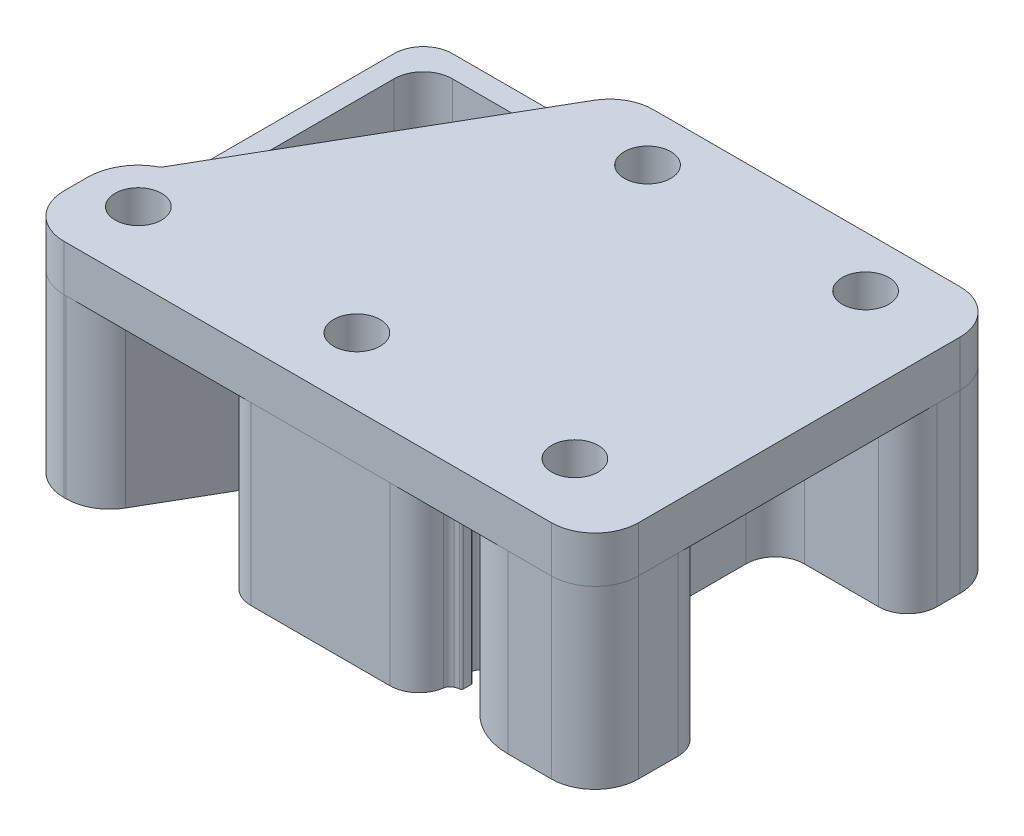
SolidWorks part; units mm, degrees
material "AISI 1045 Steel, cold drawn"
ref_plane "Front Plane" through (0, 0, 0) normal (0, 0, 1) x (1, 0, 0)
ref_plane "Top Plane" through (0, 0, 0) normal (0, 1, 0) x (1, 0, 0)
ref_plane "Right Plane" through (0, 0, 0) normal (1, 0, 0) x (0, 0, -1)
sketch "Sketch1" plane through (0, 0, 0) normal (0, 1, 0) x (1, 0, 0)
  line L0 (-13.5, -13.5) -> (-13.5, -14.619)
  line L1 (7.5, -10) -> (-7.5, -10) construction
  line L2 (7.5, -10) -> (7.5, 10) construction
  line L3 (7.5, 10) -> (-7.5, 10) construction
  line L4 (-7.5, -10) -> (-7.5, 10) construction
  line L5 (7.5, -10) -> (-7.5, 10) construction
  line L6 (7.5, 10) -> (-7.5, -10) construction
  line L7 (13.5, -13.5) -> (-13.5, -13.5) construction
  line L8 (13.5, -13.5) -> (13.5, 13.5)
  line L9 (13.5, 13.5) -> (-13.5, 13.5)
  line L10 (-13.5, -13.5) -> (-13.5, 13.5)
  line L11 (13.5, -13.5) -> (-13.5, 13.5) construction
  line L12 (13.5, 13.5) -> (-13.5, -13.5) construction
  line L13 (-13.5, -14.619) -> (13.5, -14.619)
  line L14 (13.5, -14.619) -> (13.5, -13.5)
  point P0 (0, 0)
  point P6 (0, 0)
  dimension "D1" = 15
  dimension "D2" = 27
  dimension "D3" = 1.119
  dimension "D4" = 20
extrude "Boss-Extrude1" add sketch "Sketch1" along normal mid plane 12.1
hole_wizard "M3 Clearance Hole1" positions "Sketch2" profile "Sketch3" hole size "M3" standard "ANSI Metric" end condition through all
sketch "Sketch2" plane through (0, 6.05, 0) normal (0, 1, 0) x (1, 0, 0)
  point P0 (-7.5, 10)
  point P3 (7.5, 10)
  point P6 (7.5, -10)
  point P9 (-7.5, -10)
sketch "Sketch3" plane through (-7.5, 6.05, -10) normal (1, 0, 0) x (0, 0, 1)
  line L0 (0, 0) -> (0, 12.1)
  line L1 (0, 12.1) -> (1.6, 12.1)
  line L2 (1.6, 12.1) -> (1.6, 0)
  line L5 (1.6, 0) -> (0, 0)
  line L11 (0, -6.35) -> (0, 107.95) construction
  dimension "Thru Hole Dia." = 3.2
  dimension "Thru Hole Depth" = 12.1
sketch "Sketch6" plane through (0, 6.05, 0) normal (0, 1, 0) x (1, 0, 0)
  line L0 (13.5, 13.5) -> (-13.5, 13.5) construction
  line L1 (-13.5, -14.619) -> (-28, -14.619)
  line L2 (-13.5, -14.619) -> (-13.5, 13.5)
  line L3 (-13.5, 13.5) -> (-28, 13.5)
  line L4 (-28, -14.619) -> (-28, 13.5)
  dimension "D1" = 28
extrude "Boss-Extrude3" add sketch "Sketch6" against normal up to surface (12.1 mm away) up to face at (-7.5, -6.05, -8.4)
sketch "Sketch8" plane through (0, 6.05, 0) normal (0, 1, 0) x (1, 0, 0)
  line L0 (-28, -14.619) -> (13.5, -14.619) construction
  line L2 (2.881, -10) -> (2.881, 4)
  line L3 (2.881, 4) -> (1.361, 4)
  line L4 (1.361, -14.619) -> (1.361, 4)
  line L5 (7.5, -14.619) -> (1.361, -14.619)
  arc A0 (2.881, -10) -> (7.5, -14.619) centre (7.5, -10) ccw
  dimension "D1" = 1.52
  dimension "D2" = 14
extrude "Cut-Extrude2" cut sketch "Sketch8" against normal up to surface (12.1 mm away) up to face at (-7.5, -6.05, -8.4)
sketch "Sketch9" plane through (0, 6.05, 0) normal (0, 1, 0) x (1, 0, 0)
  line L1 (2.881, 4) -> (6.306, 4)
  line L2 (2.881, 4) -> (2.881, -8)
  line L3 (2.881, -8) -> (6.306, -8)
  line L4 (6.306, 4) -> (6.306, -8)
  dimension "D1" = 3.425
  dimension "D2" = 12
extrude "Cut-Extrude3" cut sketch "Sketch9" against normal up to surface (12.1 mm away) up to face at (-7.5, -6.05, -8.4)
sketch "Sketch11" plane through (0, 6.05, 0) normal (0, 1, 0) x (1, 0, 0)
  line L1 (2.111, 0.7046) -> (2.111, 4.8734) construction
  line L4 (2.365, -998.8465) -> (2.365, 49001.1535) construction
  line L5 (2.111, 2.2598) -> (2.111, 2)
  line L6 (1.361, 3) -> (2.111, 3) construction
  line L7 (1.361, 4) -> (1.361, -14.619) construction
  line L8 (6.306, 4) -> (1.361, 4) construction
  line L9 (2.111, 2) -> (1.361, 2)
  line L10 (1.361, 2) -> (1.361, 4)
  line L11 (2.111, 4) -> (1.361, 4)
  line L12 (2.111, 3.7402) -> (2.111, 4)
  arc A2 (1.6728, 3.4989) -> (1.6728, 2.5011) centre (1.916, 3) ccw
  arc A4 (1.6728, 2.5011) -> (1.9806, 2.4085) centre (2.111, 3.4) ccw
  arc A5 (2.111, 2.2598) -> (1.9806, 2.4085) centre (1.961, 2.2598) ccw
  arc A6 (2.111, 3.7402) -> (1.9806, 3.5915) centre (1.961, 3.7402) cw
  arc A7 (1.6728, 3.4989) -> (1.9806, 3.5915) centre (2.111, 2.6) cw
  point P7 (1.361, 3)
  line M19 (1.361, -14.619) -> (1.361, 4)
  line M20 (1.361, 4) -> (6.306, 4)
  dimension "D3" = 0.555
  dimension "D4" = 1
  dimension "D5" = 1
  dimension "D6" = 0.15
  dimension "D1" = 0.254
  dimension "D2" = 0.75
  dimension "D7" = 1
extrude "Boss-Extrude4" add sketch "Sketch11" against normal up to surface (12.1 mm away) contours A2 A7 A6 L12 L10 M20 | L5 A5 A4 A2 L9 M19 region at (1.6833, 6.05, -3.7249) region at (1.6833, 6.05, -2.2751) up to face at (-7.5, -6.05, -8.4)
pattern_linear "LPattern1" count 9 spacing 2 along (0, 0, 1) of "Boss-Extrude4"
sketch "Sketch12" plane through (0, 6.05, 0) normal (0, 1, 0) x (1, 0, 0)
  circle A0 centre (2.111, 4) radius 0.5
  circle A1 centre (6.306, 4) radius 0.5
  circle A2 centre (6.306, -8) radius 0.5
  dimension "D1" = 1
extrude "Cut-Extrude5" cut sketch "Sketch12" against normal up to surface (12.1 mm away) up to face at (1.556, -6.05, 5.2005)
sketch "Sketch13" plane through (0, 6.05, 0) normal (0, 1, 0) x (1, 0, 0)
  line L3 (2.111, -14) -> (1.361, -14) construction
  line L4 (2.111, -13.7402) -> (2.111, -14) construction
  line L5 (2.111, -14) -> (1.361, -14)
  line L6 (2.111, -13.7402) -> (2.111, -14)
  line L7 (1.361, -14) -> (1.361, -13)
  arc A6 (1.6728, -12.5011) -> (1.6728, -13.4989) centre (1.916, -13) ccw construction
  arc A7 (1.6728, -13.4989) -> (1.9806, -13.5915) centre (2.111, -12.6) ccw construction
  arc A8 (2.111, -13.7402) -> (1.9806, -13.5915) centre (1.961, -13.7402) ccw construction
  arc A9 (1.361, -13) -> (1.6728, -13.4989) centre (1.916, -13) ccw
  arc A10 (1.6728, -13.4989) -> (1.9806, -13.5915) centre (2.111, -12.6) ccw
  arc A11 (2.111, -13.7402) -> (1.9806, -13.5915) centre (1.961, -13.7402) ccw
extrude "Cut-Extrude6" cut sketch "Sketch13" against normal up to surface (12.1 mm away) up to face at (1.6903, -6.05, 5.2284)
fillet "Fillet3" radius 0.5 7 edges at (5.806, 0, 8) (6.306, 0, 7.5) (5.806, 0, -4) (6.306, 0, -3.5) (2.611, 0, -4) (1.8595, 0, -3.5679) (2.881, 0, 8)
sketch "Sketch17" plane through (0, 6.05, 0) normal (0, 1, 0) x (1, 0, 0)
  line L0 (-21.1595, -14.619) -> (-15.513, -17.879)
  line L11 (-6.4019, 5.9019) -> (-3.8038, 4.4019) construction
  line L12 (-6.4019, 5.9019) -> (-2.9019, 11.9641) construction
  line L13 (-3.8038, 4.4019) -> (-0.3038, 10.4641) construction
  line L14 (-2.9019, 11.9641) -> (-0.3038, 10.4641) construction
  line L15 (-4.201, 12.7141) -> (0.9952, 9.7141) construction
  line L16 (-4.201, 12.7141) -> (-2.701, 15.3122) construction
  line L17 (0.9952, 9.7141) -> (2.4952, 12.3122) construction
  line L18 (-2.701, 15.3122) -> (2.4952, 12.3122) construction
  line L19 (-5.1029, 5.1519) -> (-0.1029, 13.8122) construction
  line L20 (-21.1595, -14.619) -> (-8.5843, 7.1619)
  line L21 (-15.513, -17.879) -> (-2.9378, 3.9019)
  line L22 (-8.5843, 7.1619) -> (-2.9378, 3.9019)
  line L23 (-22.5782, -10.8263) -> (-19.8719, -12.3888) construction
  line L24 (-22.5782, -10.8263) -> (-12.5782, 6.4942) construction
  line L25 (-19.8719, -12.3888) -> (-9.8719, 4.9317) construction
  line L26 (-12.5782, 6.4942) -> (-9.8719, 4.9317) construction
  line L27 (-28, -14.619) -> (1.361, -14.619) construction
  line L28 (-14.8719, -3.7285) -> (-17.5782, -2.166) construction
  circle A0 centre (-7.5, 10) radius 1.6 construction
  circle A1 centre (-7.5, -10) radius 1.6 construction
  dimension "D1" = 6.52
  dimension "D3" = 3
  dimension "D10" = 3
  dimension "D2" = 6
  dimension "D4" = 3
  dimension "D5" = 10
  dimension "D6" = 3.125
  dimension "D7" = 2.5
  dimension "D8" = 60
  dimension "D9" = 3
  dimension "D11" = 20
extrude "Cut-Extrude7" cut sketch "Sketch17" against normal up to surface (12.1 mm away) up to face at (1.9594, -6.05, 4.4571)
sketch "Sketch18" plane through (0, 6.05, 0) normal (0, 1, 0) x (1, 0, 0)
  line L0 (-26.0342, -14.619) -> (-26.0342, -10)
  line L2 (-14.1485, 10.3744) -> (-26.7237, -11.4065)
  line L3 (-12.344, 13.5) -> (-24.1063, -6.8729)
  line L4 (-12.344, 13.5) -> (-28, 13.5)
  line L5 (-28, 13.5) -> (-28, -14.619)
  line L7 (-28, -14.619) -> (-21.1595, -14.619) construction
  line L8 (-8.5843, 7.1619) -> (-21.1595, -14.619) construction
  line L10 (-28, -14.619) -> (-26.0342, -14.619)
  arc A2 (-24.1063, -6.8729) -> (-26.0342, -10) centre (-22.5342, -10) ccw
  point P0 (-7.5, -10)
  dimension "D2" = 3.5
  dimension "D1" = 6.425
extrude "Cut-Extrude8" cut sketch "Sketch18" against normal up to surface (12.1 mm away) contours A2 L10 | A2 L3 L4 L5 L10 region at (-22.8632, 6.05, -4.1187) up to face at (1.2277, -6.05, 4.4618)
hole_wizard "M3 Clearance Hole2" positions "Sketch19" profile "Sketch20" hole size "M3" standard "ANSI Metric" end condition up to next
sketch "Sketch19" plane through (0, 6.05, 0) normal (0, 1, 0) x (1, 0, 0)
  point P0 (-22.5342, -10)
sketch "Sketch20" plane through (-22.5342, 6.05, 10) normal (1, 0, 0) x (0, 0, 1)
  line L0 (0, 0) -> (0, 12.1)
  line L1 (0, 12.1) -> (1.6, 12.1)
  line L2 (1.6, 12.1) -> (1.6, 0)
  line L5 (1.6, 0) -> (0, 0)
  line L11 (0, -6.35) -> (0, 107.95) construction
  dimension "Thru Hole Dia." = 3.2
  dimension "Thru Hole Depth" = 12.1
fillet "Fillet4" radius 3 5 edges at (13.5, 0, 14.619) (13.5, 0, -13.5) (-12.344, 0, -13.5) (-26.0342, 0, 14.619) (-21.1595, 0, 14.619)
sketch "Sketch21" plane through (0, 6.05, 0) normal (0, 1, 0) x (1, 0, 0)
  line L0 (-8.5843, 7.1619) -> (-20.2935, -13.119) construction
  line L1 (-17.8343, -8.8595) -> (-20.8004, -7.147)
  line L2 (-17.8343, -8.8595) -> (-9.3343, 5.8629)
  line L3 (-20.8004, -7.147) -> (-12.3004, 7.5754)
  line L4 (-9.3343, 5.8629) -> (-12.3004, 7.5754)
  line L5 (-2.9378, 3.9019) -> (-8.5843, 7.1619) construction
  dimension "D3" = 17
  dimension "D1" = 3.425
  dimension "D2" = 1.5
extrude "Cut-Extrude9" cut sketch "Sketch21" against normal up to surface (12.1 mm away) up to face at (-22.5342, -6.05, 11.6)
sketch "Sketch22" plane through (0, 6.05, 0) normal (0, 1, 0) x (1, 0, 0)
  circle A0 centre (-20.8004, -7.147) radius 0.5
  circle A1 centre (-12.3004, 7.5754) radius 0.5
  circle A2 centre (-8.5843, 7.1619) radius 0.5
  circle A3 centre (-2.9378, 3.9019) radius 0.5
  arc A4 (2.544, 4.25) -> (1.6303, 3.8625) centre (2.111, 4) ccw construction
extrude "Cut-Extrude10" cut sketch "Sketch22" against normal up to surface (12.1 mm away) up to face at (-22.5342, -6.05, 11.6)
fillet "Fillet5" radius 0.5 10 edges at (-17.8343, 0, 8.8595) (-3.1878, 0, -3.4689) (-3.3708, 0, -4.1519) (-8.8343, 0, -6.7289) (-8.1513, 0, -6.9119) (-11.8674, 0, -7.3254) (-12.5504, 0, -7.1424) (-20.5504, 0, 6.714) (-20.3674, 0, 7.397) (-9.3343, 0, -5.8629)
ref_plane "Plane2" through (6.9551, 0, -12.0466) normal (0.5, 0, -0.866) x (-0.866, 0, -0.5)
sketch "Sketch29" plane through (0, 6.05, 0) normal (0, 1, 0) x (1, 0, 0)
  line L0 (-13.21, 12) -> (-24.1063, -6.8729) construction
  line L1 (-26.0342, -11.619) -> (-26.0342, -10) construction
  line L2 (13.5, -11.619) -> (13.5, 10.5) construction
  line L3 (10.5, 13.5) -> (-10.6119, 13.5) construction
  line L5 (-23.0342, -14.619) -> (10.5, -14.619)
  line L6 (-26.0342, -11.619) -> (-26.0342, -10)
  line L7 (13.5, -11.619) -> (13.5, 10.5)
  line L8 (10.5, 13.5) -> (-10.6119, 13.5)
  line L10 (-13.21, 12) -> (-24.1063, -6.8729)
  arc A0 (-24.1063, -6.8729) -> (-26.0342, -10) centre (-22.5342, -10) ccw construction
  arc A1 (-26.0342, -11.619) -> (-23.0342, -14.619) centre (-23.0342, -11.619) ccw construction
  arc A2 (10.5, -14.619) -> (13.5, -11.619) centre (10.5, -11.619) ccw construction
  arc A3 (13.5, 10.5) -> (10.5, 13.5) centre (10.5, 10.5) ccw construction
  arc A4 (-10.6119, 13.5) -> (-13.21, 12) centre (-10.6119, 10.5) ccw construction
  arc A5 (-24.1063, -6.8729) -> (-26.0342, -10) centre (-22.5342, -10) ccw
  arc A6 (-26.0342, -11.619) -> (-23.0342, -14.619) centre (-23.0342, -11.619) ccw
  arc A7 (10.5, -14.619) -> (13.5, -11.619) centre (10.5, -11.619) ccw
  arc A8 (13.5, 10.5) -> (10.5, 13.5) centre (10.5, 10.5) ccw
  arc A9 (-10.6119, 13.5) -> (-13.21, 12) centre (-10.6119, 10.5) ccw
  circle A12 centre (-22.5342, -10) radius 1.6 construction
  circle A13 centre (-7.5, -10) radius 1.6 construction
  circle A14 centre (7.5, -10) radius 1.6 construction
  circle A15 centre (7.5, 10) radius 1.6 construction
  circle A16 centre (-7.5, 10) radius 1.6 construction
  circle A17 centre (-22.5342, -10) radius 1.6
  circle A18 centre (-7.5, -10) radius 1.6
  circle A19 centre (7.5, -10) radius 1.6
  circle A20 centre (7.5, 10) radius 1.6
  circle A21 centre (-7.5, 10) radius 1.6
extrude "Boss-Extrude7" add sketch "Sketch29" along normal blind 3.175 separate body
hole_wizard "CBORE for M3 SHCS1" positions "Sketch23" profile "Sketch25" counterbore size "M3" standard "ANSI Metric" end condition up to next
sketch "Sketch23" plane through (6.9551, 0, -12.0466) normal (0.5, 0, -0.866) x (-0.866, 0, -0.5)
  line L0 (4.4952, -6.05) -> (9.4952, 6.05) construction
  line L1 (-2.3433, -6.05) -> (15.9402, -6.05) construction
  line L3 (-2.3433, 6.05) -> (15.9402, 6.05) construction
  point P15 (6.9952, 0)
  dimension "D1" = 5
sketch "Sketch25" plane through (0.8971, 0, -15.5442) normal (0, 1, 0) x (-0.866, 0, -0.5)
  line L0 (0, 0) -> (0, 12)
  line L1 (0, 12) -> (1.6, 12)
  line L3 (1.6, 12) -> (1.6, 6)
  line L4 (1.6, 6) -> (3.25, 6)
  line L5 (3.25, 6) -> (3.25, 0)
  line L7 (3.25, 0) -> (0, 0)
  line L11 (0, -6.35) -> (0, 107.95) construction
  dimension "Thru Hole Dia." = 3.2
  dimension "Thru Hole Depth" = 12
  dimension "C'Bore Dia." = 6.5
  dimension "C'Bore Depth" = 6
sketch "Sketch30" plane through (0, 6.05, 0) normal (0, 1, 0) x (1, 0, 0)
  line L1 (3.381, -8) -> (5.44, -8) construction
  line L2 (6.306, -7.134) -> (6.306, 3.134) construction
  line L3 (5.44, 4) -> (2.977, 4) construction
  line L4 (3.381, -8) -> (5.44, -8)
  line L5 (6.306, -7.134) -> (6.306, 3.134)
  line L6 (5.44, 4) -> (2.977, 4)
  line L7 (-18.0843, -9.2926) -> (-9.0843, 6.2959)
  line L8 (-20.0504, -7.5801) -> (-18.2673, -8.6095) construction
  line L9 (-12.7335, 6.8254) -> (-20.3674, -6.397) construction
  line L10 (-9.7673, 6.1129) -> (-11.5504, 7.1424) construction
  line L11 (-20.0504, -7.5801) -> (-18.2673, -8.6095)
  line L12 (-12.7335, 6.8254) -> (-20.3674, -6.397)
  line L13 (-9.7673, 6.1129) -> (-11.5504, 7.1424)
  line L14 (2.881, -8.5) -> (2.881, 4.0093)
  arc A0 (3.381, -8) -> (2.881, -8.5) centre (3.381, -8.5) ccw construction
  arc A1 (5.873, -8.25) -> (5.44, -8) centre (5.44, -8.5) ccw construction
  arc A2 (5.873, -8.25) -> (6.556, -7.567) centre (6.306, -8) ccw construction
  arc A3 (6.306, -7.134) -> (6.556, -7.567) centre (6.806, -7.134) ccw construction
  arc A4 (6.556, 3.567) -> (6.306, 3.134) centre (6.806, 3.134) ccw construction
  arc A5 (6.556, 3.567) -> (5.873, 4.25) centre (6.306, 4) ccw construction
  arc A6 (5.44, 4) -> (5.873, 4.25) centre (5.44, 4.5) ccw construction
  arc A7 (2.544, 4.25) -> (2.977, 4) centre (2.977, 4.5) ccw construction
  arc A8 (3.381, -8) -> (2.881, -8.5) centre (3.381, -8.5) ccw
  arc A9 (5.873, -8.25) -> (5.44, -8) centre (5.44, -8.5) ccw
  arc A10 (5.873, -8.25) -> (6.556, -7.567) centre (6.306, -8) ccw
  arc A11 (6.306, -7.134) -> (6.556, -7.567) centre (6.806, -7.134) ccw
  arc A12 (6.556, 3.567) -> (6.306, 3.134) centre (6.806, 3.134) ccw
  arc A13 (6.556, 3.567) -> (5.873, 4.25) centre (6.306, 4) ccw
  arc A14 (5.44, 4) -> (5.873, 4.25) centre (5.44, 4.5) ccw
  arc A15 (2.881, 4.0093) -> (2.977, 4) centre (2.977, 4.5) ccw
  arc A17 (-18.0843, -9.2926) -> (-18.2673, -8.6095) centre (-18.5173, -9.0426) ccw construction
  arc A18 (-20.0504, -7.5801) -> (-20.5504, -7.5801) centre (-20.3004, -8.0131) ccw construction
  arc A19 (-20.8004, -6.647) -> (-20.3674, -6.397) centre (-20.8004, -6.147) ccw construction
  arc A20 (-12.7335, 6.8254) -> (-12.7335, 7.3254) centre (-13.1665, 7.0754) ccw construction
  arc A21 (-11.8004, 7.5754) -> (-12.7335, 7.3254) centre (-12.3004, 7.5754) ccw construction
  arc A22 (-11.8004, 7.5754) -> (-11.5504, 7.1424) centre (-11.3004, 7.5754) ccw construction
  arc A23 (-9.7673, 6.1129) -> (-9.0843, 6.2959) centre (-9.5173, 6.5459) ccw construction
  arc A24 (-18.0843, -9.2926) -> (-18.2673, -8.6095) centre (-18.5173, -9.0426) ccw
  arc A25 (-20.0504, -7.5801) -> (-20.5504, -7.5801) centre (-20.3004, -8.0131) ccw
  arc A26 (-20.8004, -6.647) -> (-20.3674, -6.397) centre (-20.8004, -6.147) ccw
  arc A27 (-12.7335, 6.8254) -> (-12.7335, 7.3254) centre (-13.1665, 7.0754) ccw
  arc A28 (-11.8004, 7.5754) -> (-12.7335, 7.3254) centre (-12.3004, 7.5754) ccw
  arc A29 (-11.8004, 7.5754) -> (-11.5504, 7.1424) centre (-11.3004, 7.5754) ccw
  arc A30 (-9.7673, 6.1129) -> (-9.0843, 6.2959) centre (-9.5173, 6.5459) ccw
  arc A31 (-20.8004, -6.647) -> (-20.5504, -7.5801) centre (-20.8004, -7.147) ccw construction
  arc A32 (-20.8004, -6.647) -> (-20.5504, -7.5801) centre (-20.8004, -7.147) ccw
extrude "Boss-Extrude8" add sketch "Sketch30" against normal up to surface (12.1 mm away) up to face at (-22.5342, -6.05, 11.6)
fillet "Fillet6" radius 1 1 edges at (2.881, 0, -4.0093)
sketch "Sketch31" plane through (0, 6.05, 0) normal (0, 1, 0) x (1, 0, 0)
  line L0 (13.5, 6.9) -> (4.381, 6.9)
  line L2 (4.381, 6.9) -> (4.381, -6.9)
  line L3 (4.381, -6.9) -> (13.5, -6.9)
  line L4 (2.881, -10) -> (2.881, 3.4759) construction
  line L6 (13.5, 6.9) -> (13.5, -6.9)
  line L7 (13.5, -11.619) -> (13.5, 10.5) construction
  circle A0 centre (7.5, -10) radius 1.6 construction
  circle A1 centre (7.5, 10) radius 1.6 construction
  dimension "D1" = 3.1
  dimension "D2" = 3.1
  dimension "D3" = 1.5
extrude "Cut-Extrude11" cut sketch "Sketch31" against normal up to surface (12.1 mm away) up to face at (-0.8329, -6.05, 3.7569)
sketch "Sketch32" plane through (0, 6.05, 0) normal (0, 1, 0) x (1, 0, 0)
  line L0 (-10.0574, 7.6105) -> (-19.366, -8.5125)
  line L1 (-9.0173, 6.4119) -> (-20.2935, -13.119) construction
  line L2 (-13.21, 12) -> (-24.1063, -6.8729) construction
  line L3 (-13.21, 12) -> (-24.1063, -6.8729)
  line L5 (10.5, 13.5) -> (-10.6119, 13.5) construction
  line L6 (-7.5, 13.5) -> (-10.6119, 13.5)
  arc A0 (-19.366, -8.5125) -> (-24.1063, -6.8729) centre (-22.5342, -10) ccw
  arc A1 (-24.1063, -6.8729) -> (-26.0342, -10) centre (-22.5342, -10) ccw construction
  arc A2 (-7.5, 13.5) -> (-10.0574, 7.6105) centre (-7.5, 10) ccw
  arc A3 (-10.6119, 13.5) -> (-13.21, 12) centre (-10.6119, 10.5) ccw construction
  arc A4 (-10.6119, 13.5) -> (-13.21, 12) centre (-10.6119, 10.5) ccw
  dimension "D1" = 1.5
extrude "Cut-Extrude12" cut sketch "Sketch32" against normal up to surface (12.1 mm away) up to face at (-0.3561, -6.05, 3.5736)
sketch "Sketch34" plane through (0, -6.05, 0) normal (0, -1, 0) x (1, 0, 0)
  line L0 (0.111, -6.1826) -> (-7.4426, 6.9005)
  line L1 (-3.3708, -3.1519) -> (-13.6309, 14.619) construction
  line L2 (0.111, -6.1826) -> (0.111, 12.619)
  line L4 (0.111, 12.619) -> (-5.8414, 12.619)
  line L5 (2.111, 10.2598) -> (2.111, 9.7402) construction
  line L7 (-13.6309, 14.619) -> (1.361, 14.619) construction
  circle A2 centre (-7.5, 10) radius 3.1
  arc A3 (-7.4426, 6.9005) -> (-5.8414, 12.619) centre (-7.5, 10) ccw
  dimension "D2" = 1.5
  dimension "D3" = 2
  dimension "D4" = 2
  dimension "D1" = 1.5
extrude "Cut-Extrude14" cut sketch "Sketch34" against normal up to surface (12.1 mm away) up to face at (-0.2449, 6.05, 3.6119)
sketch "Sketch35" plane through (0, -6.05, 0) normal (0, -1, 0) x (1, 0, 0)
  line L0 (-4.9175, -11.9731) -> (0.7117, -8.7231) construction
  line L1 (-7.5622, -13.5) -> (1.2713, -8.4)
  line L2 (10.5, -13.5) -> (-7.5, -13.5) construction
  line L3 (1.2713, -8.4) -> (4.3871, -8.4)
  line L4 (7.5, -13.5) -> (-7.5622, -13.5)
  line L6 (4.381, -6.9) -> (13.5, -6.9) construction
  circle A1 centre (7.5, -10) radius 1.6 construction
  arc A3 (4.3871, -8.4) -> (7.5, -13.5) centre (7.5, -10) ccw
  dimension "D1" = 1.5
extrude "Cut-Extrude15" cut sketch "Sketch35" against normal up to surface (12.1 mm away) up to face at (-2.7337, 6.05, 6.3401)
fillet "Fillet7" radius 2 9 edges at (-13.6309, 0, 14.619) (1.361, 0, 14.619) (13.5, 0, 6.9) (4.381, 0, 6.9) (13.5, 0, -6.9) (4.381, 0, -6.9) (-19.366, 0, 8.5125) (-7.5612, 0, -13.4995) (-10.0574, 0, -7.6105)
fillet "Fillet8" radius 1 6 edges at (0.111, 0, 12.619) (0.111, 0, -6.1826) (-5.8414, 0, 12.619) (-7.4426, 0, 6.9005) (4.3871, 0, -8.4) (1.2713, 0, -8.4)
sketch "Sketch36" plane through (0, 6.05, 0) normal (0, 1, 0) x (1, 0, 0)
  line L0 (2.881, 4.4759) -> (2.881, 3.4759)
  line L1 (1.611, 4) -> (1.611, 4.4759)
  arc A0 (1.611, 4.4759) -> (2.881, 4.4759) centre (2.246, 4.4759) cw
  arc A3 (2.544, 4.25) -> (1.6303, 3.8625) centre (2.111, 4) ccw construction
  arc A4 (2.544, 4.25) -> (2.6117, 4.1586) centre (2.977, 4.5) ccw construction
  arc A5 (2.881, 3.4759) -> (2.6117, 4.1586) centre (1.881, 3.4759) ccw construction
  arc A6 (2.544, 4.25) -> (1.611, 4) centre (2.111, 4) ccw
  arc A7 (2.544, 4.25) -> (2.6117, 4.1586) centre (2.977, 4.5) ccw
  arc A8 (2.881, 3.4759) -> (2.6117, 4.1586) centre (1.881, 3.4759) ccw
  dimension "D1" = 1
extrude "Cut-Extrude16" cut sketch "Sketch36" against normal up to surface (12.1 mm away) up to face at (-2.9137, -6.05, 6.8822)
sketch "Sketch37" plane through (0, 6.05, 0) normal (0, 1, 0) x (1, 0, 0)
  line L0 (-10.6817, 6.5291) -> (-9.847, 7.9748)
  line L1 (-18.0522, -6.2369) -> (-10.6817, 6.5291) construction
  line L2 (1.0392, 8.534) -> (-6.9682, 13.1571) construction
  line L3 (-6.6764, 12.9886) -> (-6.9682, 13.1571)
  arc A0 (-6.6764, 12.9886) -> (-9.847, 7.9748) centre (-7.5, 10) ccw
  circle A1 centre (-7.5, 10) radius 1.6 construction
  arc A2 (-6.9682, 13.1571) -> (-8.5926, 13.3251) centre (-7.9682, 11.425) ccw construction
  arc A3 (-8.5926, 13.3251) -> (-10.6269, 8.4276) centre (-7.5, 10) ccw construction
  arc A4 (-10.6817, 6.5291) -> (-10.6269, 8.4276) centre (-12.4137, 7.5291) ccw construction
  arc A5 (-6.9682, 13.1571) -> (-8.5926, 13.3251) centre (-7.9682, 11.425) ccw
  arc A6 (-8.5926, 13.3251) -> (-10.6269, 8.4276) centre (-7.5, 10) ccw
  arc A7 (-10.6817, 6.5291) -> (-10.6269, 8.4276) centre (-12.4137, 7.5291) ccw
  dimension "D1" = 1.5
extrude "Cut-Extrude17" cut sketch "Sketch37" against normal up to surface (12.1 mm away) up to face at (-2.9137, -6.05, 6.8822)
fillet "Fillet9" radius 2 2 edges at (-6.6764, 0, -12.9886) (-9.847, 0, -7.9748)
sketch "Sketch38" plane through (0, 6.05, 0) normal (0, 1, 0) x (1, 0, 0)
  line L0 (-26.0342, -10) -> (-26.0342, 13.1)
  line L1 (-26.0342, 13.1) -> (-7.5, 13.1)
  line L2 (-24.5342, -7.1277) -> (-24.5342, 11.6)
  line L3 (-24.5342, 11.6) -> (-10.1552, 11.6)
  line L4 (-24.5342, -10) -> (-24.5342, 11.6) construction
  line L5 (-24.5342, 11.6) -> (-7.5, 11.6) construction
  arc A0 (-7.2093, 13.0863) -> (-10.3388, 8.7545) centre (-7.5, 10) ccw construction
  arc A1 (-7.5, 13.1) -> (-10.1552, 11.6) centre (-7.5, 10) ccw
  arc A2 (-20.7842, -6.9689) -> (-26.0342, -10) centre (-22.5342, -10) ccw construction
  arc A3 (-24.5342, -7.1277) -> (-26.0342, -10) centre (-22.5342, -10) ccw
  dimension "D1" = 1.5
extrude "Boss-Extrude9" add sketch "Sketch38" against normal up to surface (12.1 mm away) up to face at (-2.9137, -6.05, 6.8822)
fillet "Fillet10" radius 2 4 edges at (-24.5342, 0, 7.1277) (-10.1552, 0, -11.6) (-26.0342, 0, -13.1) (-24.5342, 0, -11.6)
sketch "Sketch39" plane through (0.9551, 0, -1.6543) normal (-0.5, 0, 0.866) x (0.866, 0, 0.5)
  circle A0 centre (-6.9952, 0) radius 1.6 construction
  circle A1 centre (-6.9952, 0) radius 1.6
extrude "Boss-Extrude10" add sketch "Sketch39" against normal up to surface (6 mm away)
